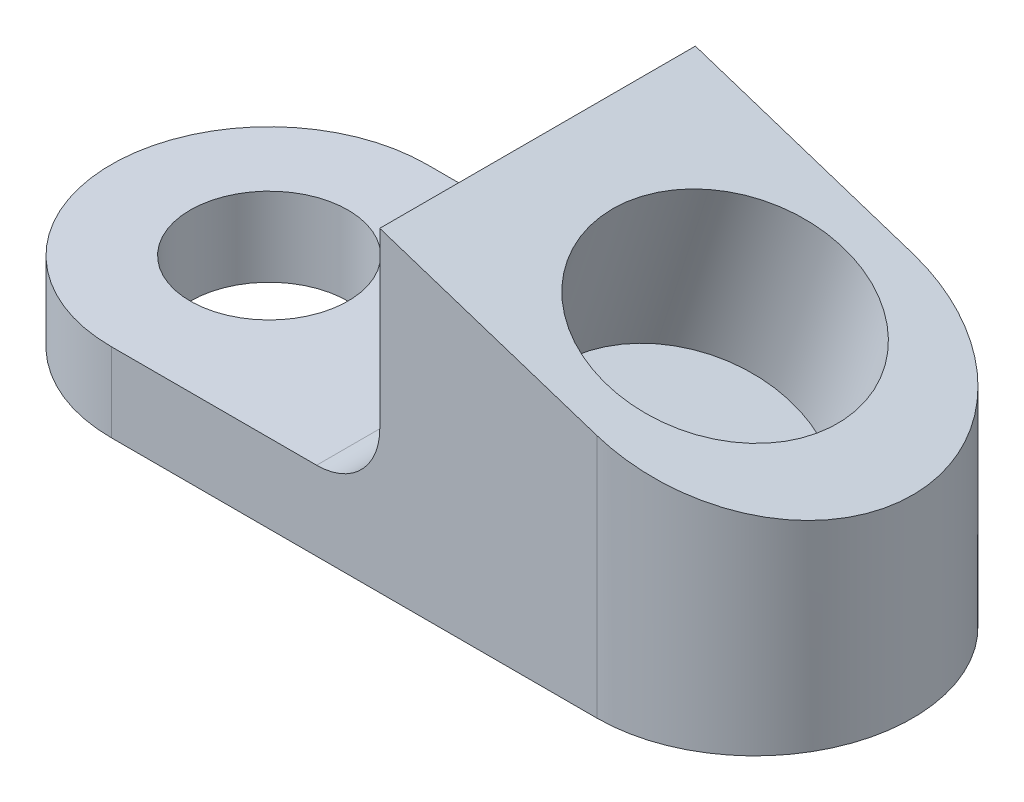
SolidWorks part; units mm, degrees
ref_plane "Front" through (0, 0, 0) normal (0, 0, 1) x (1, 0, 0)
ref_plane "Top" through (0, 0, 0) normal (0, 1, 0) x (1, 0, 0)
ref_plane "Right" through (0, 0, 0) normal (1, 0, 0) x (0, 0, -1)
sketch "Sketch1" plane through (0, 0, 0) normal (0, 0, 1) x (1, 0, 0)
  line L0 (0, 0) -> (73.3903, 0)
  line L1 (73.3903, 0) -> (73.3903, 15.5486)
  line L2 (73.3903, 15.5486) -> (43.2073, 25.4)
  line L3 (43.2073, 25.4) -> (43.2073, 6.35)
  line L4 (43.2073, 6.35) -> (0, 6.35)
  line L5 (0, 6.35) -> (0, 0)
  line L6 (21.6037, 6.35) -> (21.6037, 0) construction
  line L7 (58.2988, 20.4743) -> (49.5437, -6.35) construction
  line L8 (58.2988, 20.4743) -> (198.7687, 450.85) construction
  line L9 (198.7687, -6.35) -> (198.7687, 450.85) construction
  line L10 (198.7687, 450.85) -> (284.4937, -6.35) construction
  point P11 (54.1033, 7.62)
  point P15 (0, 0)
  point P16 (0, 0)
  point P17 (40.0089, -7.6228)
  dimension "D1" = 31.75
  dimension "D2" = 7.62
  dimension "D3" = 27.94
  dimension "D4" = 25.4
  dimension "D5" = 6.35
  dimension "D6" = 457.2
  dimension "D7" = 234.95
  dimension "D8" = 85.725
  dimension "D9" = 6.35
extrude "Boss-Extrude1" add sketch "Sketch1" along normal mid plane 25.4
sketch "Sketch2" plane through (11.6519, 35.6993, 0) normal (0.3103, 0.9506, 0) x (0.9506, -0.3103, 0)
  line L0 (33.1937, 0) -> (64.9437, 0) construction
  line L1 (33.1937, -12.7) -> (33.1937, 12.7) construction
  line L2 (64.9437, -12.7) -> (64.9437, 12.7) construction
  line L3 (49.0687, 12.7) -> (49.0687, -12.7) construction
  line L4 (64.9437, 12.7) -> (33.1937, 12.7) construction
  line L5 (64.9437, -12.7) -> (33.1937, -12.7) construction
  circle A0 centre (49.0687, 0) radius 9.525
  dimension "D1" = 19.05
extrude "Cut-Extrude1" cut sketch "Sketch2" against normal up to vertex (13.5217 mm away) up to point (54.1033, 7.62, 0)
sketch "Sketch3" plane through (0, 6.35, 0) normal (0, 1, 0) x (1, 0, 0)
  line L0 (0, 0) -> (43.2073, 0) construction
  line L1 (43.2073, -12.7) -> (43.2073, 12.7) construction
  circle A0 centre (21.6037, 0) radius 6.35
  dimension "D1" = 12.7
extrude "Cut-Extrude2" cut sketch "Sketch3" against normal through all
fillet "Fillet3" 2 edges at (73.3903, 7.7743, 12.7) (73.3903, 7.7743, -12.7) type full round first side face at (38.8659, 8.9414, 12.7) second side face at (38.8659, 8.9414, -12.7) middle face at (73.3903, 7.7743, 0)
sketch "Sketch4" plane through (0, 6.35, 0) normal (0, 1, 0) x (1, 0, 0)
  line L0 (43.2073, 12.7) -> (0, 12.7) construction
  line L5 (43.2073, 12.7) -> (0, 12.7)
  line L6 (0, 12.7) -> (0, -12.7)
  line L7 (0, -12.7) -> (43.2073, -12.7)
  line L8 (43.2073, -12.7) -> (43.2073, 12.7)
  line L9 (21.6037, 12.7) -> (0, 12.7)
  line L10 (0, 12.7) -> (0, -12.7)
  line L11 (0, -12.7) -> (21.6037, -12.7)
  arc A0 (21.6037, 12.7) -> (21.6037, -12.7) centre (21.6037, 0) ccw
  dimension "D1" = 0
extrude "Cut-Extrude3" cut sketch "Sketch4" against normal through all
fillet "Fillet4" radius 5.08 1 edges at (43.2073, 6.35, 0)
sketch "Sketch5" plane through (7.4564, 22.845, 0) normal (0.3103, 0.9506, 0) x (0.9506, -0.3103, 0)
  point P0 (49.0687, 0)
